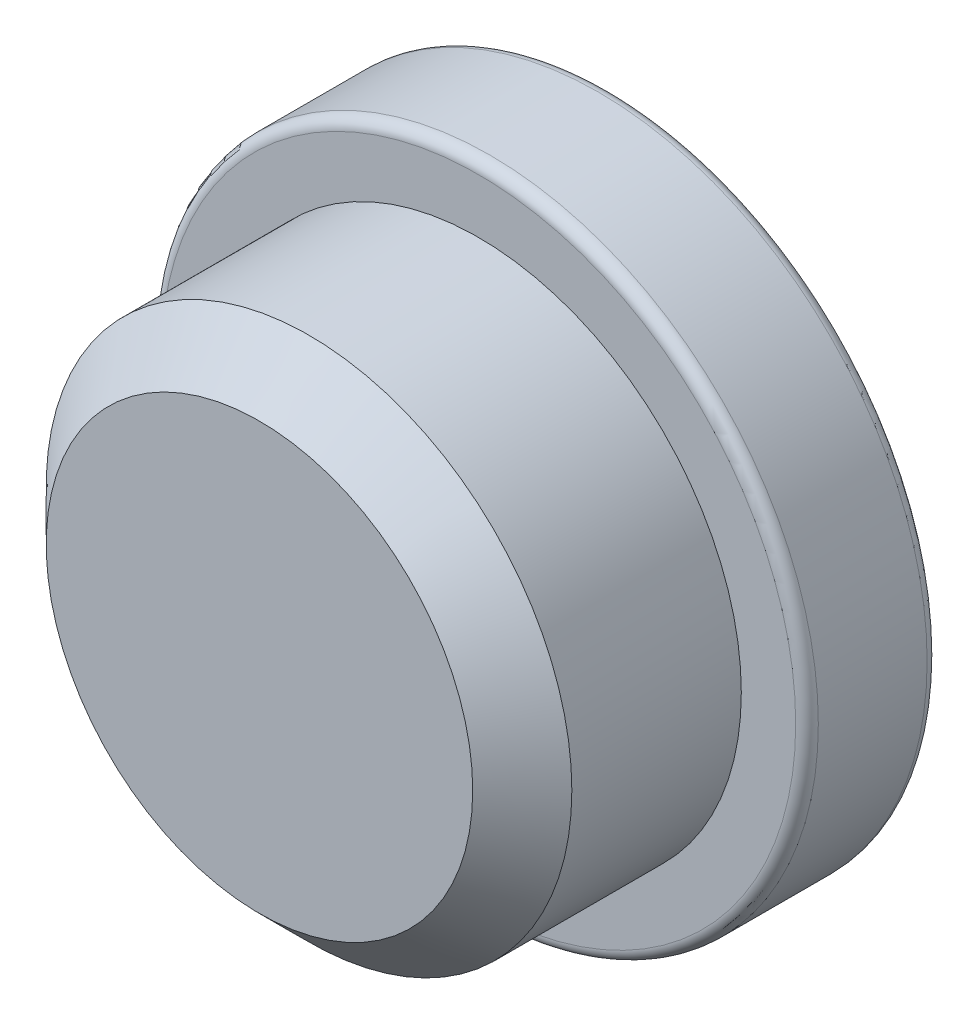
SolidWorks part; units mm, degrees
ref_plane "Front Plane" through (0, 0, 0) normal (0, 0, 1) x (1, 0, 0)
ref_plane "Top Plane" through (0, 0, 0) normal (0, 1, 0) x (1, 0, 0)
ref_plane "Right Plane" through (0, 0, 0) normal (1, 0, 0) x (0, 0, -1)
sketch "Sketch1" plane through (0, 0, 0) normal (0, 1, 0) x (1, 0, 0)
  line L0 (0, 0) -> (0, 6.35) construction
  line L1 (0, 6.35) -> (5.9531, 6.35)
  line L2 (5.9531, 6.35) -> (5.9531, 3.9687)
  line L3 (5.9531, 3.9687) -> (4.7625, 3.9687)
  line L4 (4.7625, 3.9687) -> (4.7625, 0.898)
  line L5 (4.7625, 0.898) -> (3.8645, 0)
  line L6 (3.8645, 0) -> (0, 0)
  line L7 (0, 0) -> (0, 6.35)
  dimension "D1" = 11.9062
  dimension "D2" = 9.525
  dimension "D3" = 6.35
  dimension "D4" = 2.3813
  dimension "D5" = 45
  dimension "D6" = 1.27
revolve "Revolve1" add sketch "Sketch1" angle 360 about L0
fillet "Fillet1" radius 0.2048 2 edges at (5.9531, 0, -3.9687) (5.9531, 0, -6.35)
sketch "Sketch2" plane through (0, 0, -6.35) normal (0, 0, -1) x (-1, 0, 0)
  line L1 (0.7938, -4.7625) -> (-0.7937, -4.7625)
  line L2 (0.7938, -4.7625) -> (0.7938, 4.7625)
  line L3 (0.7938, 4.7625) -> (-0.7937, 4.7625)
  line L4 (-0.7937, -4.7625) -> (-0.7937, 4.7625)
  line L5 (0.7938, -4.7625) -> (-0.7937, 4.7625) construction
  line L6 (0.7938, 4.7625) -> (-0.7937, -4.7625) construction
  point P0 (0, 0)
  dimension "D1" = 1.5875
  dimension "D2" = 9.525
extrude "Cut-Extrude1" cut sketch "Sketch2" against normal blind 0.3969
chamfer "Chamfer1" distance 0.7937 angle 60 2 edges at (0, -4.7625, -5.9531) (0, 4.7625, -5.9531) first distance on face at (0, -4.7625, -6.1516) first distance on face at (0, 4.7625, -6.1516)
